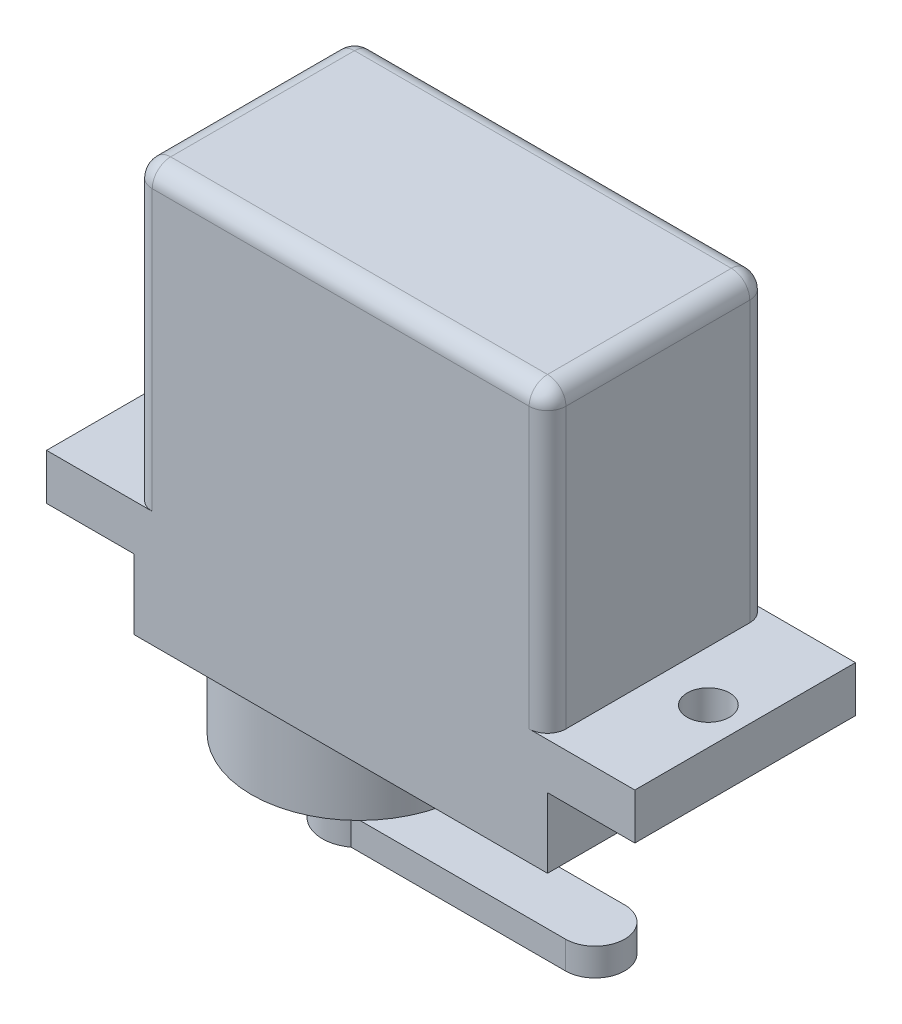
SolidWorks part; units mm, degrees
material "有机玻璃"
ref_plane "前视" through (0, 0, 0) normal (0, 0, 1) x (1, 0, 0)
ref_plane "上视" through (0, 0, 0) normal (0, 1, 0) x (1, 0, 0)
ref_plane "右视" through (0, 0, 0) normal (1, 0, 0) x (0, 0, -1)
sketch "草图1" plane through (0, 0, 0) normal (0, 0, 1) x (1, 0, 0)
  line L0 (0, 0) -> (0, 61.6949) construction
  line L1 (0, 0) -> (-11.25, 0)
  line L2 (-11.25, 0) -> (-11.25, 3.8)
  line L3 (-11.25, 3.8) -> (-16, 3.8)
  line L4 (-16, 3.8) -> (-16, 6.3)
  line L5 (-16, 6.3) -> (-11.25, 6.3)
  line L6 (-11.25, 6.3) -> (-11.25, 22.5)
  line L7 (-11.25, 22.5) -> (11.25, 22.5)
  line L8 (11.25, 22.5) -> (11.25, 6.3)
  line L9 (11.25, 6.3) -> (16, 6.3)
  line L10 (16, 6.3) -> (16, 3.8)
  line L11 (16, 3.8) -> (11.25, 3.8)
  line L12 (11.25, 3.8) -> (11.25, 0)
  line L13 (11.25, 0) -> (0, 0)
  point P5 (0, 1.1024)
  dimension "D1" = 22.5
  dimension "D2" = 3.8
  dimension "D3" = 2.5
  dimension "D4" = 32
  dimension "D5" = 22.5
extrude "凸台-拉伸1" add sketch "草图1" along normal mid plane 12
sketch "草图2" plane through (0, 3.8, 0) normal (0, -1, 0) x (1, 0, 0)
  line L0 (-16, 0) -> (16, 0) construction
  line L1 (-16, 6) -> (-16, -6) construction
  line L2 (16, 6) -> (16, -6) construction
  line L3 (0, 0) -> (0, 8.3558) construction
  circle A0 centre (-14, 0) radius 1.15
  circle A1 centre (14, 0) radius 1.15
  dimension "D1" = 28
  dimension "D2" = 2.3
extrude "切除-拉伸1" cut sketch "草图2" against normal through all
sketch "草图3" plane through (0, 0, 0) normal (0, -1, 0) x (1, 0, 0)
  line L0 (0, 0) -> (-11.25, 0) construction
  line L1 (-11.25, 6) -> (-11.25, -6) construction
  circle A0 centre (-5, 0) radius 5.85
  point P7 (-6.1165, 0)
  dimension "D1" = 11.7
  dimension "D2" = 5
extrude "凸台-拉伸2" add sketch "草图3" along normal blind 4.5
sketch "草图4" plane through (0, -4.5, 0) normal (0, -1, 0) x (1, 0, 0)
  circle A0 centre (-5, 0) radius 2
  dimension "D1" = 4
extrude "凸台-拉伸3" add sketch "草图4" along normal blind 4
sketch "草图5" plane through (0, -8.5, 0) normal (0, -1, 0) x (1, 0, 0)
  line L0 (-5, 0) -> (7.8379, 0) construction
  line L1 (-5, 1.6115) -> (7.8379, 1.6115)
  line L2 (-5, -1.6115) -> (7.8379, -1.6115)
  arc A0 (-5, 1.6115) -> (-5, -1.6115) centre (-5, 0) ccw
  arc A1 (7.8379, -1.6115) -> (7.8379, 1.6115) centre (7.8379, 0) ccw
  point P4 (1.419, 0)
extrude "凸台-拉伸4" add sketch "草图5" against normal blind 1.5
fillet "圆角1" radius 1 8 edges at (11.25, 22.5, 0) (0, 22.5, 6) (-11.25, 22.5, 0) (0, 22.5, -6) (-11.25, 14.4, -6) (11.25, 14.4, -6) (11.25, 14.4, 6) (-11.25, 14.4, 6)
